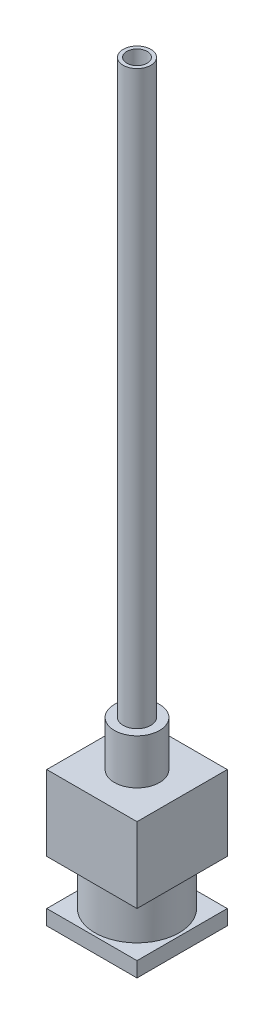
SolidWorks part; units mm, degrees
ref_plane "Front Plane" through (0, 0, 0) normal (0, 0, 1) x (1, 0, 0)
ref_plane "Top Plane" through (0, 0, 0) normal (0, 1, 0) x (1, 0, 0)
ref_plane "Right Plane" through (0, 0, 0) normal (1, 0, 0) x (0, 0, -1)
sketch "Sketch1" plane through (0, 0, 0) normal (0, 1, 0) x (1, 0, 0)
  line L1 (3, -3) -> (-3, -3)
  line L2 (3, -3) -> (3, 3)
  line L3 (3, 3) -> (-3, 3)
  line L4 (-3, -3) -> (-3, 3)
  line L5 (0, 3) -> (0, -3) construction
  line L6 (3, 0) -> (-3, 0) construction
  point P0 (0, 0)
  dimension "D1" = 6
  dimension "D2" = 6
extrude "Boss-Extrude1" add sketch "Sketch1" along normal blind 9
sketch "Sketch2" plane through (0, 9, 0) normal (0, 1, 0) x (1, 0, 0)
  circle A0 centre (0, 0) radius 1.5
  dimension "D1" = 3
extrude "Boss-Extrude2" add sketch "Sketch2" along normal blind 3
sketch "Sketch3" plane through (0, 12, 0) normal (0, 1, 0) x (1, 0, 0)
  circle A0 centre (0, 0) radius 0.68
  circle A1 centre (0, 0) radius 0.92
  dimension "D1" = 1.36
  dimension "D2" = 1.84
extrude "Cut-Extrude1" cut sketch "Sketch3" against normal through all both and the other way through all contours A0
extrude "Boss-Extrude3" add sketch "Sketch3<3>" along normal blind 38
sketch "Sketch3<3>" plane through (0, 12, 0) normal (0, 1, 0) x (1, 0, 0) same geometry as "Sketch3"
sketch "Sketch4" plane through (0, 0, 0) normal (0, -1, 0) x (1, 0, 0)
  circle A1 centre (0, 0) radius 2
  dimension "D1" = 4
extrude "Cut-Extrude2" cut sketch "Sketch4" against normal blind 8
sketch "Sketch6" plane through (0, 0, 0) normal (0, -1, 0) x (1, 0, 0)
  line L4 (-3, 3) -> (-3, -3)
  line L5 (-3, -3) -> (3, -3)
  line L6 (3, -3) -> (3, 3)
  line L7 (3, 3) -> (-3, 3)
  line L8 (-3, 3) -> (-3, -3)
  line L9 (-3, -3) -> (3, -3)
  line L10 (3, -3) -> (3, 3)
  line L11 (3, 3) -> (-3, 3)
  circle A0 centre (0, 0) radius 2.8
  dimension "D1" = 5.6
  dimension "D2" = 0
extrude "Cut-Extrude3" cut sketch "Sketch6" against normal offset from surface (3 mm away) 4 from offset 1 up to face at (0, 0, -2) offset against normal yes
